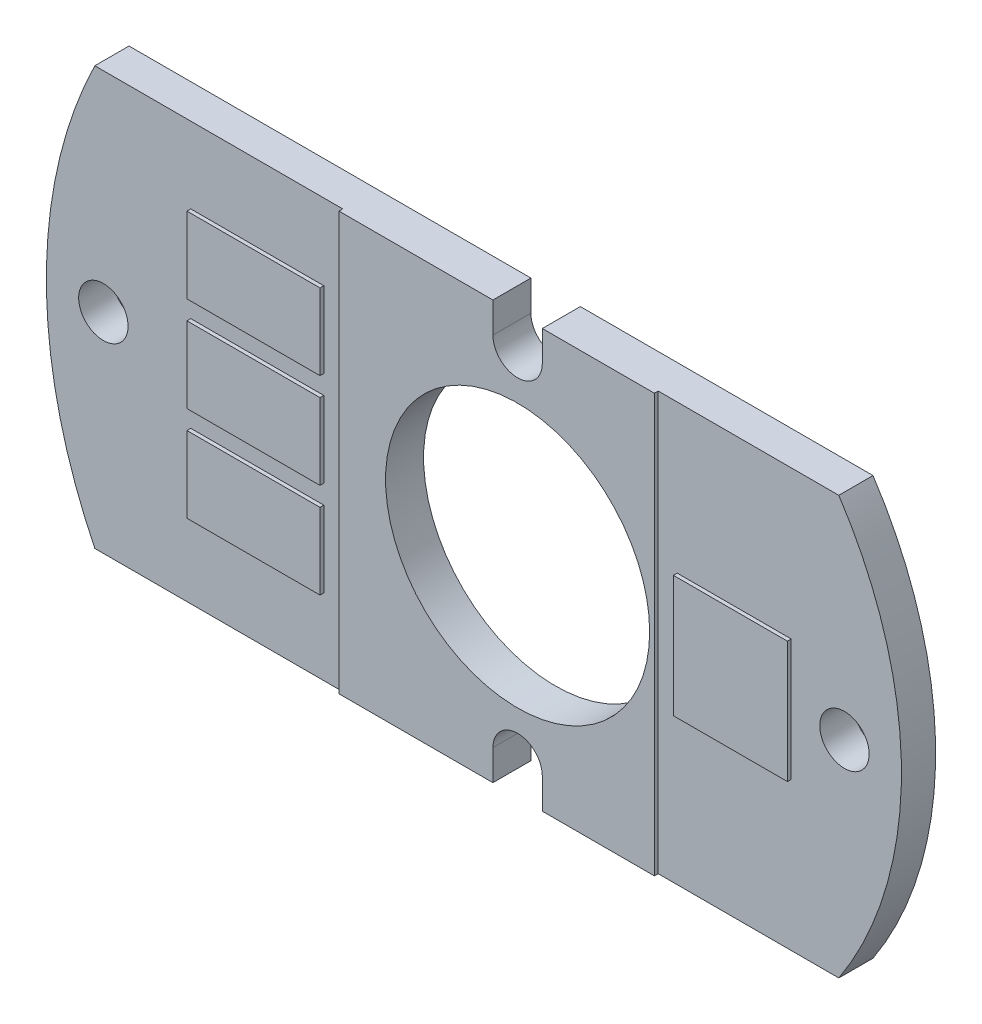
SolidWorks part; units mm, degrees
ref_plane "Спереди" through (0, 0, 0) normal (0, 0, 1) x (1, 0, 0)
ref_plane "Сверху" through (0, 0, 0) normal (0, 1, 0) x (1, 0, 0)
ref_plane "Справа" through (0, 0, 0) normal (1, 0, 0) x (0, 0, -1)
sketch "Model" plane through (0, 0, 0) normal (0, 0, 1) x (1, 0, 0)
  line L0 (1025.0386, -772.2) -> (1025.0386, -762.8) construction
  line L1 (1024.3886, -762.8) -> (1024.3886, -762)
  line L2 (1025.0386, -767.5) -> (1014.0386, -767.5) construction
  line L3 (1025.6886, -762.8) -> (1025.6886, -762)
  line L4 (1025.0386, -767.5) -> (1033.5386, -767.5) construction
  line L5 (1012.5386, -762) -> (1012.5386, -773)
  line L6 (1023.9386, -767.5) -> (1031.8639, -767.5) construction
  line L7 (1035.0386, -762) -> (1035.0386, -773)
  line L8 (1012.5386, -762) -> (1024.3886, -762)
  line L9 (1012.5386, -773) -> (1024.3886, -773)
  line L12 (1024.3886, -762.8) -> (1024.3886, -762)
  line L13 (1025.6886, -762.8) -> (1025.6886, -762)
  line L14 (1025.6886, -772.2) -> (1025.6886, -773)
  line L15 (1024.3886, -772.2) -> (1024.3886, -773)
  line L16 (1025.6886, -772.2) -> (1025.6886, -773)
  line L17 (1024.3886, -772.2) -> (1024.3886, -773)
  line L19 (1025.6886, -773) -> (1035.0386, -773)
  line L20 (1025.6886, -762) -> (1035.0386, -762)
  arc A0 (1024.3886, -762.8) -> (1025.6886, -762.8) centre (1025.0386, -762.8) ccw
  circle A1 centre (1033.5386, -767.5) radius 0.65
  circle A25 centre (1025.0386, -767.5) radius 3.4746
  arc A28 (1024.3886, -772.2) -> (1025.6886, -772.2) centre (1025.0386, -772.2) cw
  circle A33 centre (1014.0386, -767.5) radius 0.65
  point P27 (1012.0386, -767.5)
  point P45 (1036.5386, -767.5)
  dimension "D1" = 9.4
  dimension "D6" = 11
  dimension "D2" = 12.5
  dimension "D8" = 10
  dimension "D9" = 8.5
extrude "Бобышка-Вытянуть1" add sketch "Model" along normal mid plane 1 contours A25 region at (1025.0386, -763.7005, 0)
sketch "Sketch2" plane through (0, 0, 0.5) normal (0, 0, 1) x (1, 0, 0)
  line L2 (1029.2386, -760.837) -> (1037.2386, -760.837)
  line L3 (1037.2386, -760.837) -> (1037.2386, -770.1)
  line L4 (1025.0386, -767.5) -> (1032.1386, -767.5)
  line L5 (1037.2386, -774.163) -> (1037.2386, -770.1)
  line L6 (1029.2386, -774.163) -> (1037.2386, -774.163)
  line L9 (1016.3386, -769) -> (1016.3386, -770.1)
  line L10 (1016.0386, -760.614) -> (1011.6405, -760.614)
  line L11 (1011.6405, -760.614) -> (1011.6405, -770.1)
  line L12 (1019.8386, -766) -> (1019.8386, -764)
  line L13 (1019.8386, -760.837) -> (1020.3386, -760.837)
  line L14 (1020.3386, -760.837) -> (1020.3386, -764)
  line L15 (1019.8386, -760.837) -> (1016.0386, -760.614)
  line L16 (1016.3386, -766.5) -> (1016.3386, -768.5)
  line L22 (1016.3386, -764.9) -> (1016.3386, -766)
  line L23 (1016.3386, -766) -> (1019.8386, -766)
  line L24 (1020.3386, -766) -> (1020.3386, -769)
  line L25 (1019.8386, -769) -> (1016.3386, -769)
  line L26 (1016.3386, -766.5) -> (1019.8386, -766.5)
  line L27 (1019.8386, -766.5) -> (1019.8386, -768.5)
  line L28 (1019.8386, -768.5) -> (1016.3386, -768.5)
  line L30 (1016.3386, -764.9) -> (1016.3386, -764)
  line L31 (1016.3386, -764) -> (1019.8386, -764)
  line L32 (1020.3386, -764) -> (1020.3386, -766)
  line L33 (1020.3386, -771) -> (1020.3386, -769)
  line L34 (1016.3386, -771) -> (1019.8386, -771)
  line L35 (1016.3386, -770.1) -> (1016.3386, -771)
  line L37 (1016.3386, -769) -> (1019.8386, -769)
  line L39 (1019.8386, -774.163) -> (1016.0386, -774.3861)
  line L40 (1020.3386, -774.163) -> (1020.3386, -771)
  line L41 (1019.8386, -774.163) -> (1020.3386, -774.163)
  line L42 (1019.8386, -769) -> (1019.8386, -771)
  line L43 (1011.6405, -774.3861) -> (1011.6405, -770.1)
  line L44 (1016.0386, -774.3861) -> (1011.6405, -774.3861)
  line L46 (1032.1386, -769.1) -> (1032.1386, -765.9)
  line L47 (1032.1386, -765.9) -> (1029.1386, -765.9)
  line L48 (1029.1386, -765.9) -> (1029.1386, -769.1)
  line L49 (1032.1386, -769.1) -> (1029.1386, -769.1)
  line L50 (1029.1386, -767.5) -> (1028.6386, -767.5)
  line L51 (1028.6386, -767.5) -> (1028.6386, -760.837)
  line L52 (1028.6386, -767.5) -> (1028.6386, -774.163)
  line L53 (1028.6386, -774.163) -> (1029.2386, -774.163)
  line L54 (1028.6386, -760.837) -> (1029.2386, -760.837)
  line L55 (1032.1386, -769.1) -> (1032.1386, -765.9)
  point P55 (1029.1386, -767.5)
  circle M96 centre (1014.0386, -767.5) radius 0.65
  circle M97 centre (1033.5386, -767.5) radius 0.65
  line M99 (1024.3886, -762) -> (1012.5386, -762)
  line M101 (1012.5386, -773) -> (1024.3886, -773)
  line M105 (1025.6886, -773) -> (1035.0386, -773)
  line M106 (1035.0386, -773) -> (1035.0386, -762)
  line M107 (1035.0386, -762) -> (1025.6886, -762)
extrude "Extrude2" cut sketch "Sketch2" against normal blind 0.1 contours L40 L33 L24 L32 L14 L30 L31 L12 L23 L22 L27 L28 L16 L26 L25 L42 L34 L35 L9 M101 M99 M96 | L52 L51 L48 L47 L46 L49 M105 M106 M107 M97 region at (1031.8386, -762.1273, 0.5) region at (1015.5269, -767.5, 0.5)
sketch "Sketch1" plane through (0, 0, 0) normal (0, 0, 1) x (1, 0, 0)
  line L1 (1007.0641, -757.6348) -> (1015.9587, -757.6348)
  line L2 (1007.0641, -757.6348) -> (1007.0641, -780.0125)
  line L3 (1007.0641, -780.0125) -> (1015.9587, -780.0125)
  line L4 (1015.9587, -757.6348) -> (1015.9587, -780.0125)
  line L5 (1032.1104, -759.1851) -> (1040.5347, -759.1851)
  line L6 (1032.1104, -759.1851) -> (1032.1104, -777.2931)
  line L7 (1032.1104, -777.2931) -> (1040.5347, -777.2931)
  line L8 (1040.5347, -759.1851) -> (1040.5347, -777.2931)
  circle A0 centre (1025.0386, -767.5) radius 12.5
  circle A1 centre (1025.0386, -767.5) radius 10
extrude "Extrude1" cut sketch "Sketch1" against normal through all both and the other way through all contours A0 L4 L1 L2 L3 | A1 L6 L7 A0 L5 | A0 L7 L8 L5 region at (1010.7319, -769.1606, 0) region at (1036.5435, -763.1186, 0) region at (1038.2508, -768.7097, 0)
